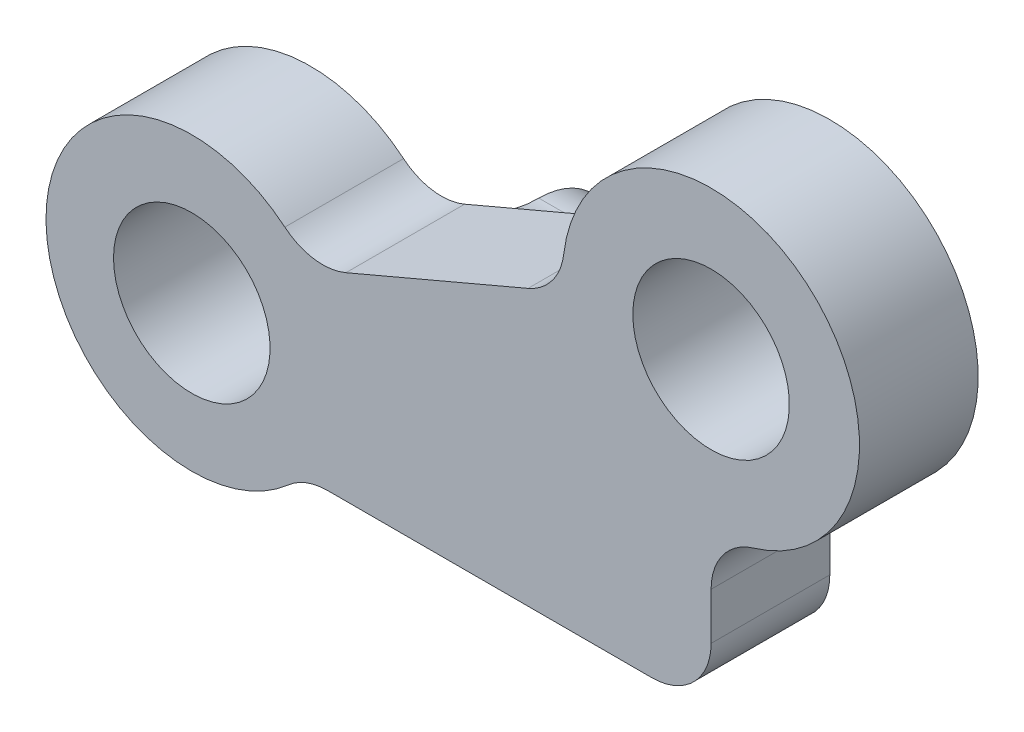
SolidWorks part; units mm, degrees
material "PLA"
ref_plane "Front Plane" through (0, 0, 0) normal (0, 0, 1) x (1, 0, 0)
ref_plane "Top Plane" through (0, 0, 0) normal (0, 1, 0) x (1, 0, 0)
ref_plane "Right Plane" through (0, 0, 0) normal (1, 0, 0) x (0, 0, -1)
ref_plane "Plane3" through (0, 0, 0) normal (0, 0, -1) x (-1, 0, 0)
sketch "Sketch17" plane through (0, 0, 0) normal (0, 0, -1) x (-1, 0, 0)
  line L0 (-43.2731, 29.4209) -> (-51.8645, 33.076)
  line L1 (-56.8391, 28.5799) -> (-56.8391, 23.2923)
  line L2 (-56.8391, 23.2923) -> (-43.0826, 23.2923)
  arc A0 (-43.0826, 23.2923) -> (-43.2731, 29.4209) centre (-39.3406, 26.4759) ccw
  arc A1 (-51.8645, 33.076) -> (-56.8391, 28.5799) centre (-56.8391, 33.5799) ccw
extrude "Boss-Extrude3" add sketch "Sketch17" against normal blind 4
hole_wizard "Hole3" positions "Sketch19" profile "Sketch18" legacy
sketch "Sketch19" plane through (0, 0, 0) normal (0, 0, -1) x (-1, 0, 0)
  point P0 (-39.3406, 26.4759)
  point P1 (-56.8391, 33.5799)
sketch "Sketch18" plane through (39.3406, 26.4759, 0) normal (1, 0, 0) x (0, 1, 0)
  line L0 (0, 0) -> (0, 4)
  line L1 (0, 4) -> (2.6375, 4)
  line L2 (2.6375, 4) -> (2.6375, 0)
  line L3 (2.6375, 0) -> (0, 0)
  line L4 (0, 110) -> (0, -10) construction
  dimension "Diameter" = 5.275
  dimension "Depth" = 4
fillet "Fillet3" radius 2 5 edges at (51.8645, 33.076, 2) (43.0826, 23.2923, 2) (43.2731, 29.4209, 2) (56.8391, 23.2923, 2) (56.8391, 28.5799, 2) tangent propagation no
ref_plane "Plane4" through (45, 0, 0) normal (1, 0, 0) x (0, 0, -1)
ref_plane "Plane5" through (47, 0, 0) normal (1, 0, 0) x (0, 0, -1)
sketch "Sketch25" plane through (47, 0, 0) normal (1, 0, 0) x (0, 0, -1)
  line L0 (0, 23.2923) -> (0, 30.1441)
  line L1 (0, 28.7883) -> (0, 38.5799) construction
  circle A0 centre (2.034, 26.8496) radius 1.5065
  arc A1 (2.034, 24.3496) -> (2.034, 29.3496) centre (2.034, 26.8496) ccw
  spline S0 degree 2 poles (2.034, 29.3496) (0.8443, 29.3488) (0, 30.1441) knots 0 0 0 1 1 1
  spline S1 degree 2 poles (2.034, 24.3496) (0.7258, 24.3594) (0, 23.2923) knots 0 0 0 1 1 1
extrude "Boss-Extrude4" add sketch "Sketch25" against normal up to surface (2 mm away) up to plane "Plane4"
